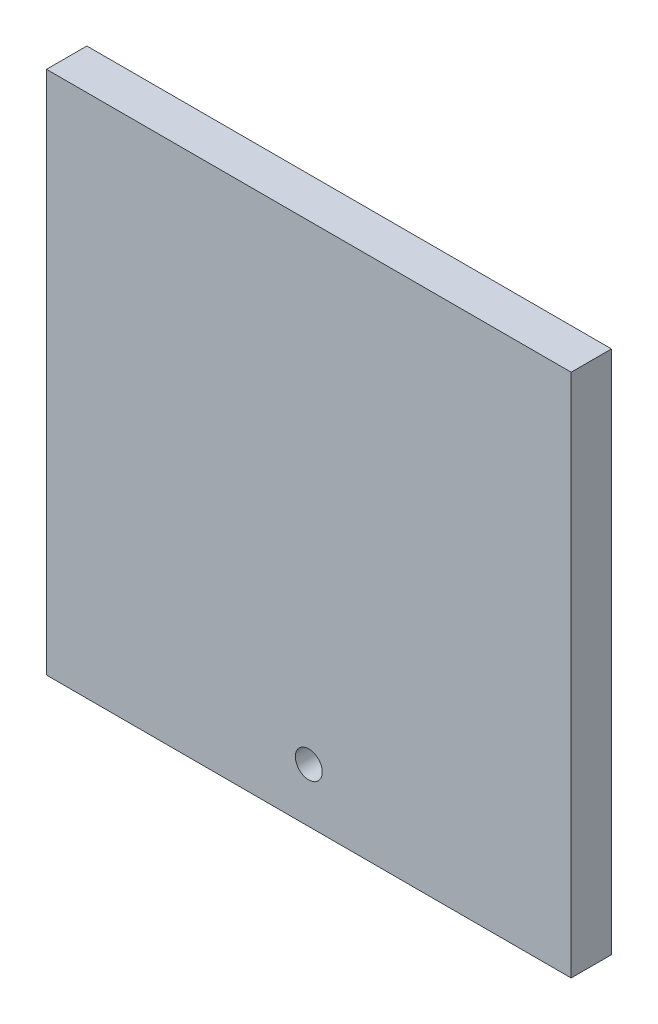
SolidWorks part; units mm, degrees
material "Maple"
ref_plane "Front Plane" through (0, 0, 0) normal (0, 0, 1) x (1, 0, 0)
ref_plane "Top Plane" through (0, 0, 0) normal (0, 1, 0) x (1, 0, 0)
ref_plane "Right Plane" through (0, 0, 0) normal (1, 0, 0) x (0, 0, -1)
sketch "Sketch1" plane through (0, 0, 0) normal (0, 0, 1) x (1, 0, 0)
  line L1 (-39, -39) -> (39, -39)
  line L2 (-39, -39) -> (-39, 39)
  line L3 (-39, 39) -> (39, 39)
  line L4 (39, -39) -> (39, 39)
  line L5 (-39, -39) -> (39, 39) construction
  line L6 (-39, 39) -> (39, -39) construction
  point P0 (0, 0)
  dimension "D1" = 78
  dimension "D2" = 78
extrude "Boss-Extrude1" add sketch "Sketch1" along normal blind 6
sketch "Sketch2" plane through (0, 0, 0) normal (0, 0, -1) x (-1, 0, 0)
  line L0 (39, -39) -> (-39, -39) construction
  circle A0 centre (0, -31) radius 2
  dimension "D1" = 4
  dimension "D2" = 8
extrude "Cut-Extrude1" cut sketch "Sketch2" against normal through all
